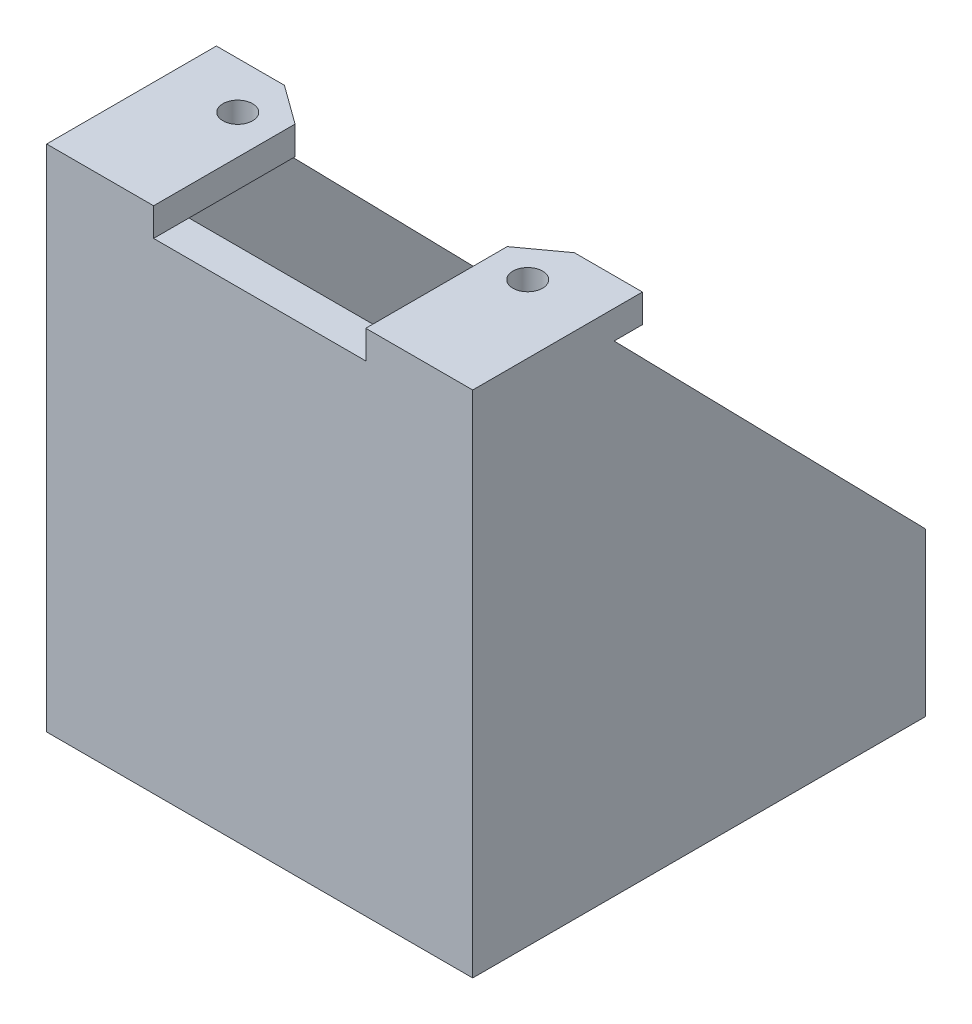
SolidWorks part; units mm, degrees
ref_plane "Front Plane" through (0, 0, 0) normal (0, 0, 1) x (1, 0, 0)
ref_plane "Top Plane" through (0, 0, 0) normal (0, 1, 0) x (1, 0, 0)
ref_plane "Right Plane" through (0, 0, 0) normal (1, 0, 0) x (0, 0, -1)
sketch "Sketch2" plane through (0, 0, 0) normal (0, 1, 0) x (1, 0, 0)
  line L0 (15.061, 0) -> (15.061, 32)
  line L1 (-12.561, 2.5) -> (12.561, 2.5)
  line L2 (-12.561, 2.5) -> (-12.561, 32)
  line L4 (12.561, 2.5) -> (12.561, 32)
  line L5 (15.061, 32) -> (12.561, 32)
  line L7 (-15.061, 32) -> (-15.061, 0)
  line L8 (-15.061, 0) -> (15.061, 0)
  line L10 (-15.061, 32) -> (-12.561, 32)
  point P4 (0, 2.5)
  point P12 (0, 0)
  dimension "D1" = 2.5
  dimension "D2" = 2.5
  dimension "D3" = 29.5
  dimension "D4" = 25.122
extrude "Boss-Extrude1" add sketch "Sketch2" along normal blind 32.5
sketch "Sketch3" plane through (15.061, 0, 0) normal (1, 0, 0) x (0, 0, -1)
  line L0 (32, 10) -> (10, 32.5)
  line L3 (10, 32.5) -> (32, 32.5)
  line L4 (32, 32.5) -> (32, 10)
  line L5 (0, 55) -> (0, -55) construction
  line L6 (32, 32.5) -> (32, 0) construction
  line L7 (0, 0) -> (32, 0) construction
  line L8 (0, 32.5) -> (32, 32.5) construction
  dimension "D1" = 10
  dimension "D2" = 10
extrude "Cut-Extrude1" cut sketch "Sketch3" against normal through all
sketch "Sketch4" plane through (0, 0, 0) normal (0, -1, 0) x (1, 0, 0)
  line L0 (-15.061, 0) -> (-15.061, -32)
  line L2 (-15.061, -32) -> (-10.061, -32)
  line L4 (-7.5, -6) -> (7.5, -6)
  line L6 (10.061, -32) -> (15.061, -32)
  line L8 (15.061, -32) -> (15.061, 0)
  line L9 (15.061, 0) -> (-15.061, 0)
  line L10 (15.061, 0) -> (15.061, -32) construction
  line L13 (-12.561, -2.5) -> (-12.561, -32) construction
  line L18 (-12.561, -10) -> (-7.5, -6)
  line L20 (-12.561, -10) -> (-12.561, -20)
  line L21 (-12.561, -20) -> (-7.061, -29)
  line L23 (12.561, -32) -> (12.561, -2.5) construction
  line L24 (12.561, -10) -> (12.561, -20)
  line L25 (12.561, -20) -> (7.061, -29)
  line L26 (12.561, -10) -> (7.5, -6)
  arc A0 (7.061, -29) -> (10.061, -32) centre (10.061, -29) ccw
  arc A1 (-10.061, -32) -> (-7.061, -29) centre (-10.061, -29) ccw
  circle A2 centre (-10.2499, -4.95) radius 1.05
  circle A3 centre (-10.2499, -29.4) radius 1.05
  circle A4 centre (10.2499, -29.4) radius 1.05
  circle A5 centre (10.2499, -4.95) radius 1.05
  point P7 (-9.6139, -7.5)
  point P8 (-7.3658, -5.8722)
  point P17 (7.061, -32)
  point P20 (-7.061, -32)
  point P29 (0, 0)
  point P31 (0, -6)
  dimension "D4" = 3
  dimension "D5" = 2.1
  dimension "D10" = 15
  dimension "D11" = 10
  dimension "D1" = 8
  dimension "D2" = 6
  dimension "D3" = 32
  dimension "D6" = 4.8111
  dimension "D7" = 4.95
  dimension "D8" = 4.8111
  dimension "D9" = 29.4
  dimension "D12" = 20
  dimension "D13" = 8
  dimension "D14" = 5
  dimension "D15" = 8
  dimension "D16" = 20.122
extrude "Boss-Extrude2" add sketch "Sketch4" along normal blind 1.5
sketch "Sketch5" plane through (0, 32.5, 0) normal (0, 1, 0) x (1, 0, 0)
  line L10 (-15.061, 12) -> (-10.2499, 12)
  line L11 (-10.2499, 12) -> (-7.5, 10)
  line L12 (-7.5, 10) -> (-7.5, 0)
  line L13 (-15.061, 0) -> (15.061, 0) construction
  line L14 (-7.5, 0) -> (-15.061, 0)
  line L15 (-15.061, 0) -> (-15.061, 12)
  line L16 (15.061, 12) -> (10.2499, 12)
  line L17 (10.2499, 12) -> (7.5, 10)
  line L18 (7.5, 10) -> (7.5, 0)
  line L19 (7.5, 0) -> (15.061, 0)
  line L20 (15.061, 0) -> (15.061, 12)
  circle A0 centre (-10.2499, 4.95) radius 1.05 construction
  circle A1 centre (-10.2499, 8.7) radius 1.05
  circle A2 centre (10.2499, 8.7) radius 1.05
  point P4 (0, 0)
  point P5 (-12.561, 17.7581)
  point P18 (0, 0)
  point P19 (0, 0)
  point P20 (0, 0)
  point P21 (0, 0)
  point P22 (-5.4824, 0)
  point P23 (0, 0)
  point P24 (-7.3435, 9.2759)
  point P25 (0, 0)
  point P28 (0, 0)
  point P29 (0, 0)
  point P30 (-12.561, 13.2857)
  dimension "D4" = 0
  dimension "D1" = 8.7
  dimension "D2" = 15
  dimension "D3" = 20.4998
  dimension "D5" = 10
  dimension "D6" = 12
extrude "Boss-Extrude3" add sketch "Sketch5" along normal blind 2
